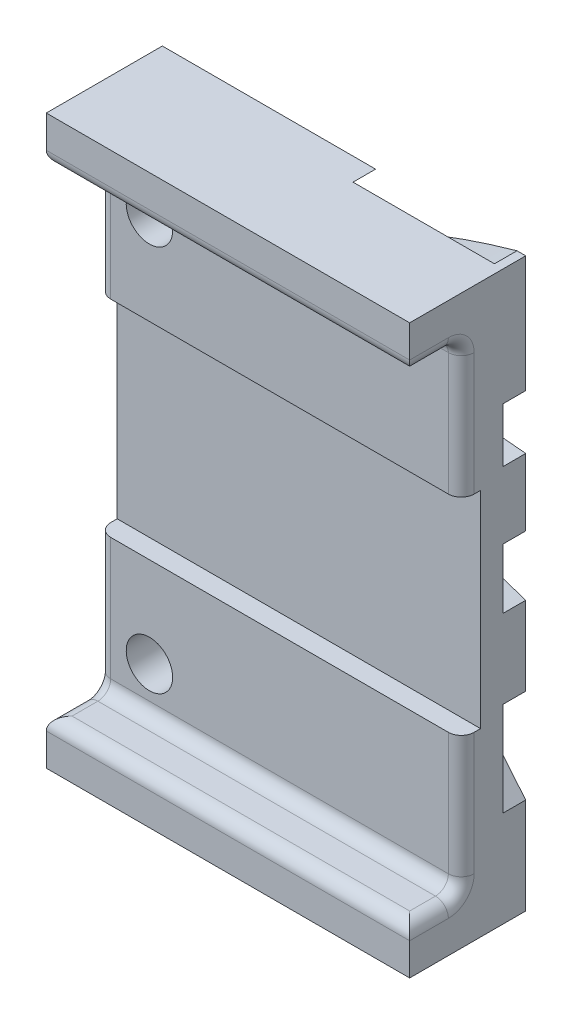
SolidWorks part; units mm, degrees
ref_plane "Front Plane" through (0, 0, 0) normal (0, 0, 1) x (1, 0, 0)
ref_plane "Top Plane" through (0, 0, 0) normal (0, 1, 0) x (1, 0, 0)
ref_plane "Right Plane" through (0, 0, 0) normal (1, 0, 0) x (0, 0, -1)
sketch "Sketch1" plane through (0, 0, 0) normal (0, 0, 1) x (1, 0, 0)
  line L1 (-14.09, -22) -> (14.09, -22)
  line L2 (-14.09, -22) -> (-14.09, 22)
  line L3 (-14.09, 22) -> (14.09, 22)
  line L4 (14.09, -22) -> (14.09, 22)
  line L5 (-14.09, -22) -> (14.09, 22) construction
  line L6 (-14.09, 22) -> (14.09, -22) construction
  point P0 (0, 0)
  dimension "D1" = 44
  dimension "D2" = 28.18
extrude "Boss-Extrude1" add sketch "Sketch1" along normal blind 11 and the other way blind 2
sketch "Sketch3" plane through (-14.09, 0, 0) normal (-1, 0, 0) x (0, 0, 1)
  line L0 (8, 8) -> (11, 8)
  line L5 (8, 18.5) -> (3, 18.5)
  line L6 (8, 18.5) -> (8, 8)
  line L7 (8, -18.5) -> (3, -18.5)
  line L8 (3, 18.5) -> (3, 8)
  line L9 (11, -8) -> (8, -8)
  line L10 (8, -8) -> (8, -18.5)
  line L13 (3, -8) -> (1.5034, -8)
  line L14 (11, 8) -> (11, -8)
  line L15 (14.8907, 0) -> (-5.9971, 0) construction
  line L16 (3, 8) -> (1.5034, 8)
  line L17 (1.5034, 8) -> (1.5034, -8)
  line L18 (3, -8) -> (3, -18.5)
  dimension "D1" = 3
  dimension "D2" = 5
  dimension "D3" = 37
extrude "Cut-Extrude1" cut sketch "Sketch3" against normal blind 37
sketch "Sketch4" plane through (0, -22, 0) normal (0, -1, 0) x (1, 0, 0)
  line L0 (-14.09, 11) -> (14.09, 11) construction
  line L1 (-6.09, 11) -> (14.09, 11)
  line L2 (-6.09, 11) -> (-6.09, 7)
  line L3 (-6.09, 7) -> (14.09, 7)
  line L4 (14.09, 11) -> (14.09, 7)
  line L5 (14.09, -2) -> (14.09, 11) construction
  line L6 (-14.09, -2) -> (-14.09, 11) construction
  dimension "D1" = 4
  dimension "D2" = 8
extrude "Cut-Extrude2" cut sketch "Sketch4" against normal blind 48
sketch "Sketch5" plane through (0, 0, -2) normal (0, 0, -1) x (-1, 0, 0)
  line L0 (14.09, 4.4317) -> (14.09, 4.2995)
  line L1 (-14.09, 22) -> (14.09, 22) construction
  line L2 (-2.4482, 22) -> (-13.4131, 22)
  line L3 (14.09, 4.4317) -> (14.09, 4.2995)
  line L4 (5.5922, -22) -> (0.0012, -22)
  line L5 (-14.09, 12.9435) -> (-14.09, 8.7272)
  line L6 (-2.4482, 22) -> (-13.4131, 22)
  line L7 (5.5922, -22) -> (0.0012, -22)
  line L8 (-5.5133, -22) -> (-9.4224, -22)
  line L9 (-14.09, 12.9435) -> (-14.09, 8.7272)
  line L10 (-14.09, 3.5233) -> (-14.09, -1.1313)
  line L11 (-14.09, -7.2405) -> (-14.09, -14.5457)
  line L12 (-5.5133, -22) -> (-9.4224, -22)
  line L13 (14.09, 22) -> (14.09, -22) construction
  line L14 (14.09, -22) -> (-14.09, -22) construction
  line L15 (-14.09, -22) -> (-14.09, 22) construction
  spline S0 degree 3 poles (-2.4482, 22) (19.5671, 11.5364) (5.1516, -7.6222) (5.5922, -22) knots 0 0 0 0 0.832841 0.832841 0.832841 0.832841
  spline S1 degree 3 poles (-13.4131, 22) (18.4961, 13.0475) (3.5462, -4.8632) (0.0012, -22) knots 0 0 0 0 0.886772 0.886772 0.886772 0.886772
  spline S2 degree 3 poles (-14.09, 12.9435) (17.0272, 14.2309) (-0.9132, -5.6377) (-5.5133, -22) knots 0 0 0 0 0.882154 0.882154 0.882154 0.882154
  spline S3 degree 3 poles (-14.09, 8.7272) (12.7104, 11.6786) (-5.2505, -7.0269) (-9.4224, -22) knots 0 0 0 0 0.871233 0.871233 0.871233 0.871233
  spline S4 degree 2 poles (-14.09, 3.5233) (7.9134, 11.6377) (-14.09, -14.5457) knots 0 0 0 1 1 1
  spline S5 degree 2 poles (-14.09, -1.1313) (-1.6541, 3.2119) (-14.09, -7.2405) knots 0 0 0 1 1 1
  line M1 (-14.09, 22) -> (-14.09, -22)
  line M2 (-14.09, -22) -> (14.09, -22)
  line M4 (14.09, 22) -> (-14.09, 22)
extrude "Cut-Extrude3" cut sketch "Sketch5" against normal blind 1.75 contours S3 S2 M1 M2 | S5 S4 M1 | S1 S0 M4 M2 region at (-9.2495, 2.4628, -2) region at (7.4678, -21.6069, -2) region at (4.526, -0.8216, -2)
sketch "Sketch7" plane through (0, 0, 11) normal (0, 0, 1) x (1, 0, 0)
  line L0 (-23.1576, 15) -> (2.9776, 15) construction
  line L1 (-6.09, 22) -> (-14.09, 22) construction
  line L2 (-14.09, 8) -> (-6.09, 8) construction
  line L3 (-31.6118, 0) -> (31.371, 0) construction
  line L4 (-10.09, 22.9416) -> (-10.09, 7.5663) construction
  line L5 (-6.09, 22) -> (-6.09, 8) construction
  line L6 (-14.09, 22) -> (-14.09, 8) construction
  circle A0 centre (-10.09, 15) radius 1.8
  circle A1 centre (-10.09, -15) radius 1.8
  point P15 (-10.09, 15)
  dimension "D1" = 3.6
extrude "Cut-Extrude4" cut sketch "Sketch7" against normal blind 23
sketch "Sketch8" plane through (0, 0, -2) normal (0, 0, -1) x (-1, 0, 0)
  circle A0 centre (10.09, -15) radius 3.25
  circle A1 centre (10.09, 15) radius 3.25
  dimension "D1" = 6.5
extrude "Cut-Extrude5" cut sketch "Sketch8" against normal blind 1.75
sketch "Sketch10" plane through (0, 22, 0) normal (0, 1, 0) x (1, 0, 0)
  line L1 (-4.8142, -11.586) -> (-16.61, -11.586)
  line L2 (-4.8142, -11.586) -> (-4.8142, -7)
  line L3 (-4.8142, -7) -> (-16.61, -7)
  line L4 (-16.61, -11.586) -> (-16.61, -7)
  line L5 (14.09, -7) -> (-6.09, -7) construction
extrude "Cut-Extrude7" cut sketch "Sketch10" against normal blind 53
fillet "Fillet1" radius 1 12 edges at (-14.09, -13.25, 3) (14.09, -13.25, 3) (14.09, 13.25, 3) (-14.09, 13.25, 3) (-14.09, -18.5, 5) (0, -18.5, 3) (14.09, -18.5, 5) (0, -18.5, 7) (14.09, 18.5, 5) (0, 18.5, 3) (-14.09, 18.5, 5) (0, 18.5, 7)
